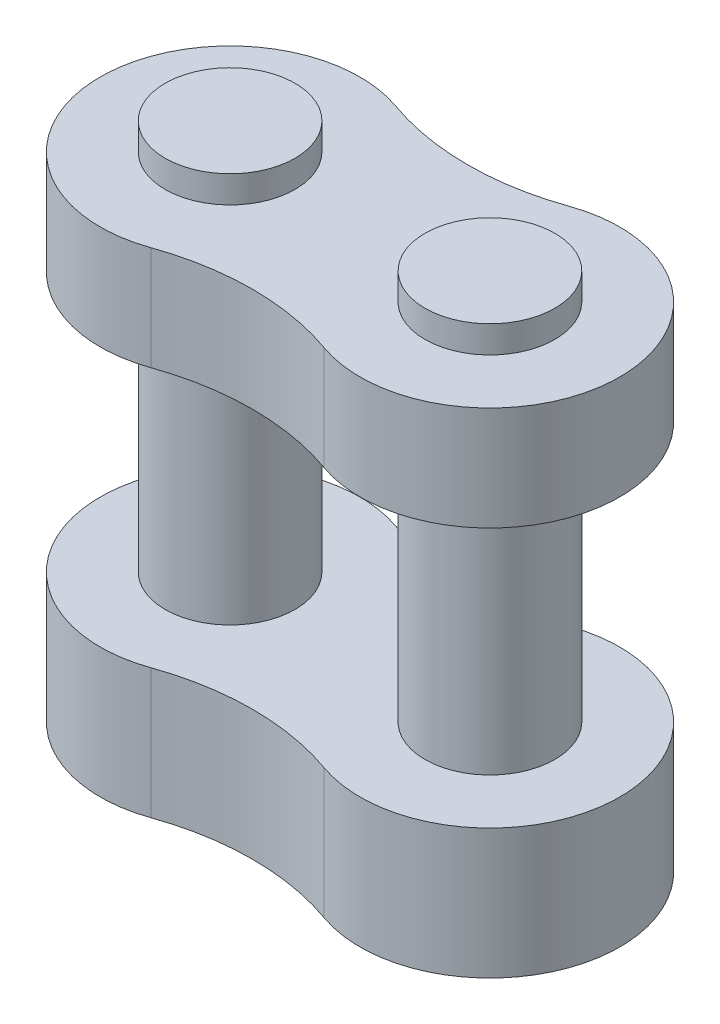
SolidWorks part; units mm, degrees
ref_plane "Front Plane" through (0, 0, 0) normal (0, 0, 1) x (1, 0, 0)
ref_plane "Top Plane" through (0, 0, 0) normal (0, 1, 0) x (1, 0, 0)
ref_plane "Right Plane" through (0, 0, 0) normal (1, 0, 0) x (0, 0, -1)
sketch "Sketch1" plane through (0, 0, 0) normal (0, 1, 0) x (1, 0, 0)
  line L0 (0, 0) -> (-6.35, 0) construction
  circle A0 centre (-6.35, 0) radius 1.1557
  circle A1 centre (0, 0) radius 1.1557
  circle A2 centre (-6.35, 0) radius 1.5875
  circle A3 centre (0, 0) radius 1.5875
  arc A4 (-5.2917, -2.9934) -> (-5.2917, 2.9934) centre (-6.35, 0) cw
  arc A5 (-1.0583, -2.9934) -> (-1.0583, 2.9934) centre (0, 0) ccw
  arc A6 (-5.2917, 2.9934) -> (-1.0583, 2.9934) centre (-3.175, 8.9803) ccw
  arc A7 (-5.2917, -2.9934) -> (-1.0583, -2.9934) centre (-3.175, -8.9803) cw
  point P12 (-3.175, 0)
  point P13 (0, 0)
  dimension "D2" = 2.3114
  dimension "D3" = 2.3114
  dimension "D4" = 3.175
  dimension "D5" = 3.175
  dimension "D6" = 3.175
  dimension "D7" = 3.175
  dimension "D8" = 6.35
  dimension "D9" = 6.35
  dimension "D1" = 6.35
extrude "Boss-Extrude1" add sketch "Sketch1" along normal blind 2.54 contours A4 A7 A5 A6 A3 A2 region at (-3.175, 0, 0)
extrude "Boss-Extrude2" add sketch "Sketch1<4>" along normal blind 3.2004 and the other way blind 6.35 contours A2 A0 | A3 | A0 region at (-7.8926, 0, 0)
sketch "Sketch1<4>" plane through (0, 0, 0) normal (0, 1, 0) x (1, 0, 0) same geometry as "Sketch1"
sketch "Sketch2" plane through (0, -6.35, 0) normal (0, -1, 0) x (1, 0, 0)
  circle A0 centre (0, 0) radius 1.5875
  circle A1 centre (-6.3348, 0) radius 1.6052
  arc A2 (-5.2917, 2.9934) -> (-5.2917, -2.9934) centre (-6.35, 0) ccw
  arc A3 (-1.0583, 2.9934) -> (-1.0583, -2.9934) centre (0, 0) cw
  arc A4 (-5.2917, 2.9934) -> (-1.0583, 2.9934) centre (-3.175, 8.9803) ccw
  arc A5 (-5.2917, -2.9934) -> (-1.0583, -2.9934) centre (-3.175, -8.9803) cw
  dimension "D1" = 3.175
  dimension "D2" = 3.2104
  dimension "D4" = 3.175
  dimension "D3" = 6.3348
extrude "Boss-Extrude3" add sketch "Sketch2" along normal blind 3.175 separate body contours A5 A3 A4 A2
